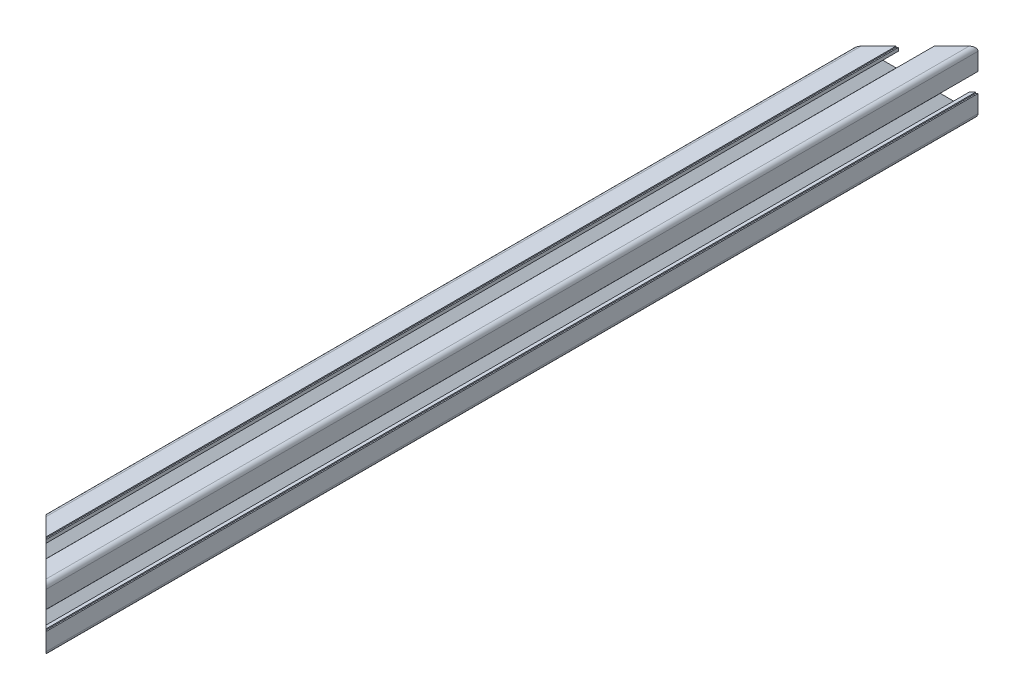
SolidWorks part; units mm, degrees
material "6061-T6 (SS)"
ref_plane "Front Plane" through (0, 0, 0) normal (0, 0, 1) x (1, 0, 0)
ref_plane "Top Plane" through (0, 0, 0) normal (0, 1, 0) x (1, 0, 0)
ref_plane "Right Plane" through (0, 0, 0) normal (1, 0, 0) x (0, 0, -1)
sketch "Sketch2" plane through (0, 0, 0) normal (0, 0, 1) x (1, 0, 0)
  line L0 (0, 15) -> (0, -15) construction
  line L1 (-15, 0) -> (15, 0) construction
  line L2 (4, -15) -> (15, -15)
  line L3 (15, -15) -> (15, -4)
  line L4 (4, -15) -> (4, -12.885)
  line L6 (8.25, -9.7455) -> (4.5045, -6)
  line L7 (0, 0) -> (15, -15) construction
  line L8 (15, -4) -> (12.885, -4)
  line L11 (4.55, -15) -> (4.55, -14.45) construction
  line L12 (4, -12.885) -> (8.25, -12.885)
  line L13 (8.25, -12.885) -> (8.25, -9.7455)
  line L14 (4.55, -14.45) -> (4, -14.45) construction
  line L15 (14.45, -4) -> (14.45, -4.55) construction
  line L16 (14.45, -4.55) -> (15, -4.55) construction
  line L17 (12.885, -4) -> (12.885, -8.25)
  line L18 (12.885, -8.25) -> (9.7455, -8.25)
  line L19 (9.7455, -8.25) -> (6, -4.5045)
  line L20 (7.8728, -6.3772) -> (6.3772, -7.8728) construction
  line L21 (11.625, -13.875) -> (11.625, -15) construction
  line L22 (9.375, -13.875) -> (13.875, -13.875)
  line L23 (9.375, -13.875) -> (9.375, -9.375)
  line L24 (9.375, -9.375) -> (13.875, -9.375)
  line L25 (13.875, -13.875) -> (13.875, -9.375)
  line L26 (11.625, -9.375) -> (11.625, -13.875) construction
  line L27 (9.375, -11.625) -> (13.875, -11.625) construction
  line L28 (13.875, -11.625) -> (15, -11.625) construction
  line L29 (8.25, -12.885) -> (9.375, -12.885) construction
  line L30 (4.5045, -6) -> (0.6555, -6)
  line L31 (0.6555, -6) -> (0, -5.45)
  line L32 (0, -6) -> (0, -5.45) construction
  circle A0 centre (0, 0) radius 3.5
  arc A2 (9.375, -12.885) -> (10.365, -13.875) centre (10.365, -12.885) ccw construction
  point P8 (0, -6)
  point P15 (4.55, -15)
  point P16 (7.125, -7.125)
  point P33 (11.625, -11.625)
  dimension "Center Hole Diameter" = 7
  dimension "Rail Height" = 30
  dimension "Rail Width" = 30
  dimension "T-Slot Width" = 8
  dimension "Slot Depth" = 9
  dimension "Slot Inner Width" = 16.5
  dimension "Step Width" = 9.1
  dimension "D1" = 1.125
  dimension "D2" = 2.115
  dimension "D3" = 50
sketch "Sketch3" plane through (0, 0, 0) normal (1, 0, 0) x (0, 0, -1)
  line L0 (-76.2, -15) -> (76.2, -15) construction
  line L1 (-50.8, 0) -> (50.8, 0) construction
  dimension "D1" = 25.4
  dimension "Length" = 152.4
sketch "Sketch4" plane through (0, 0, 0) normal (0, 0, 1) x (1, 0, 0)
  line L22 (0, -5.45) -> (0.6555, -6)
  line L23 (0.6555, -6) -> (4.5045, -6)
  line L24 (4.5045, -6) -> (8.25, -9.7455)
  line L25 (8.25, -9.7455) -> (8.25, -12.885)
  line L26 (8.25, -12.885) -> (4, -12.885)
  line L27 (4, -12.885) -> (4, -14.45)
  line L28 (4, -14.45) -> (4.55, -14.45)
  line L29 (4.55, -14.45) -> (4.55, -15)
  line L30 (4.55, -15) -> (12.885, -15)
  line L31 (4, -15) -> (15, -15) construction
  line L32 (15, -15) -> (15, -4) construction
  line L33 (15, -12.885) -> (15, -4.55)
  line L34 (15, -4.55) -> (14.45, -4.55)
  line L35 (14.45, -4.55) -> (14.45, -4)
  line L36 (14.45, -4) -> (12.885, -4)
  line L37 (12.885, -4) -> (12.885, -8.25)
  line L38 (12.885, -8.25) -> (9.7455, -8.25)
  line L39 (9.7455, -8.25) -> (6, -4.5045)
  line L40 (6, -4.5045) -> (6, -0.6555)
  line L41 (6, -0.6555) -> (5.45, 0)
  line L42 (-15, 0) -> (15, 0) construction
  line L43 (0, -5.45) -> (0, -3.5)
  line L44 (0, 15) -> (0, -15) construction
  line L45 (3.5, 0) -> (5.45, 0)
  line L46 (1.8108, -2.9952) -> (3.4913, -4.6757)
  line L47 (3.4913, -4.6757) -> (4.6757, -3.4913)
  line L48 (4.6757, -3.4913) -> (2.9952, -1.8108)
  line L49 (0, 0) -> (15, -15) construction
  line L50 (9.375, -13.875) -> (13.875, -13.875) construction
  line L51 (13.875, -13.875) -> (13.875, -9.375) construction
  line L52 (9.375, -13.875) -> (9.375, -9.375) construction
  line L53 (9.375, -9.375) -> (13.875, -9.375) construction
  line L54 (9.375, -10.365) -> (9.375, -12.885)
  line L55 (10.365, -13.875) -> (12.885, -13.875)
  line L56 (13.875, -12.885) -> (13.875, -10.365)
  line L57 (10.365, -9.375) -> (12.885, -9.375)
  arc A12 (12.885, -15) -> (15, -12.885) centre (12.885, -12.885) ccw
  circle A13 centre (0, 0) radius 3.5 construction
  arc A14 (0, -3.5) -> (1.8108, -2.9952) centre (0, 0) ccw
  arc A15 (3.5, 0) -> (2.9952, -1.8108) centre (0, 0) cw
  circle A16 centre (0, 0) radius 5.775 construction
  arc A17 (9.375, -12.885) -> (10.365, -13.875) centre (10.365, -12.885) ccw
  arc A18 (9.375, -12.885) -> (10.365, -13.875) centre (10.365, -12.885) ccw construction
  arc A19 (12.885, -13.875) -> (13.875, -12.885) centre (12.885, -12.885) ccw
  arc A20 (9.375, -10.365) -> (10.365, -9.375) centre (10.365, -10.365) cw
  arc A21 (12.885, -9.375) -> (13.875, -10.365) centre (12.885, -10.365) cw
  point P40 (4.0835, -4.0835)
  dimension "D1" = 11.55
  dimension "D2" = 0.22
extrude "Boss-Extrude1" add sketch "Sketch4" along normal blind 444.5
mirror "Mirror1" about plane through (0, 0, 0) normal (1, 0, 0) of bodies 134
mirror "Mirror2" about plane through (0, 0, 0) normal (0, 1, 0) of bodies 135
sketch "Sketch5" plane through (0, 0, 444.5) normal (0, 0, 1) x (1, 0, 0)
  line L0 (-5.675, 12.885) -> (-5.4, 13.16)
  line L1 (-8.25, 12.885) -> (-4, 12.885) construction
  line L2 (-5.4, 13.16) -> (-5.125, 12.885)
  line L3 (0, 15) -> (0, -15) construction
  line L4 (-5.675, 12.885) -> (-5.125, 12.885)
  dimension "D1" = 0.275
  dimension "D2" = 5.4
extrude "Cut-Extrude1" cut sketch "Sketch5" against normal through all both and the other way through all
sketch "Sketch6" plane through (0, -15, 0) normal (0, -1, 0) x (1, 0, 0)
  line L0 (15, 444.5) -> (-15, 444.5)
  line L1 (-15, 444.5) -> (-15, 414.5)
  line L2 (-15, 444.5) -> (-15, 0) construction
  line L3 (-15, 414.5) -> (15, 444.5)
  line L4 (15, 0) -> (-15, 0)
  line L5 (-15, 0) -> (-15, 30)
  line L6 (-15, 30) -> (15, 0)
  dimension "D1" = 45
  dimension "D2" = 45
extrude "Cut-Extrude2" cut sketch "Sketch6" against normal through all contours L6 L4 L5 | L0 L1 L3
equation "\"D1@Sketch2\"= \"Slot Depth@Sketch2\" * 0.125"
equation "\"D2@Sketch2\"=\"Slot Depth@Sketch2\"*0.235"
equation "\"D1@Sketch4\"=\"Center Hole Diameter@Sketch2\"*1.65"
equation "\"D2@Sketch4\"=(\"Step Width@Sketch2\"-\"T-Slot Width@Sketch2\")*0.2"
equation "\"D1@Sketch5\"=(\"Step Width@Sketch2\"-\"T-Slot Width@Sketch2\")*0.5*0.5"
equation "\"D2@Sketch5\"=\"T-Slot Width@Sketch2\"*1.35*0.5"
equation "\"altitude_horizontal_rail_length\"=10in"
equation "\"altitude_vertictal_rail_length\"=12in"
equation "\"table_length\"=72in"
equation "\"table_width\"=25in"
equation "\"table_thickness\"=1.75in"
equation "\"azimuth_horizontal_rail_length\"=(\"altitude_horizontal_rail_length\"+6in-0.29in)"
equation "\"azimuth_vertictal_rail_length_short\"=(\"altitude_vertictal_rail_length\"-5in)"
equation "\"azimuth_vertictal_rail_length_long\"=(\"azimuth_vertictal_rail_length_short\"+4in)"
equation "\"azimuth_mounting_hole_distance\"=9in"
equation "\"table_frame_vertical_length\"=12.5in"
equation "\"table_frame_diagonal_length\"=17.5in"
equation "\"D1@Boss-Extrude1\"=\"table_frame_diagonal_length\""
